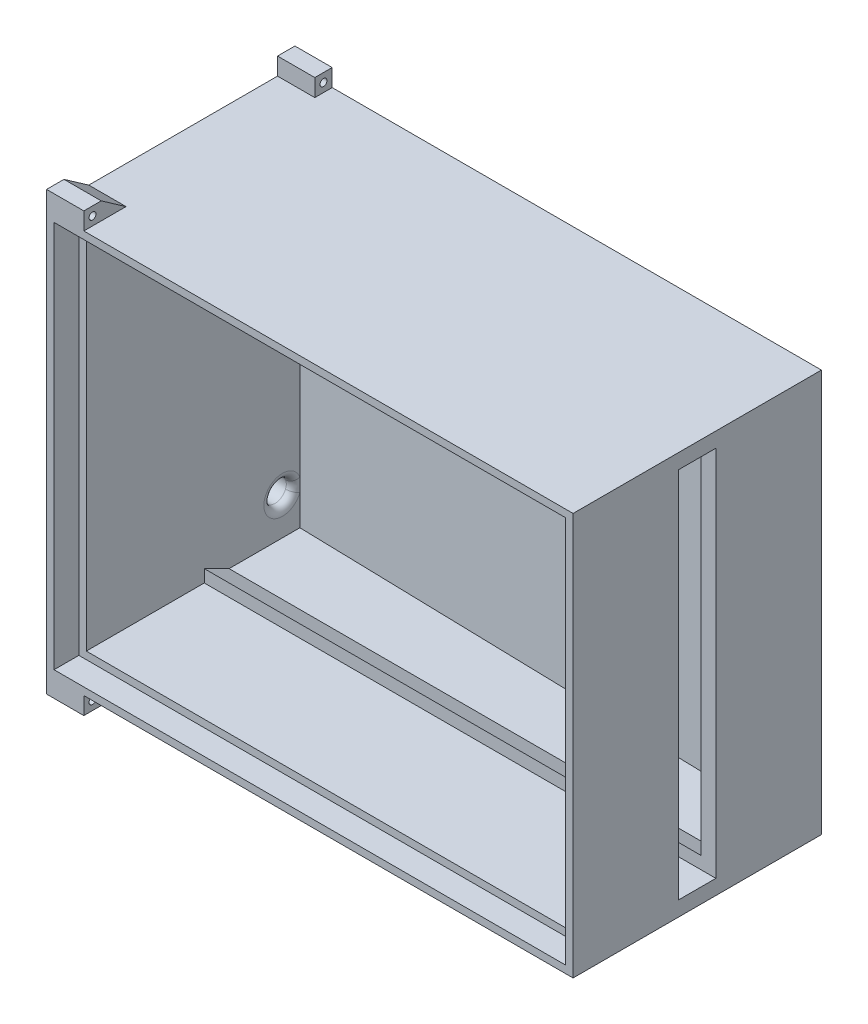
SolidWorks part; units mm, degrees
ref_plane "Front Plane" through (0, 0, 0) normal (0, 0, 1) x (1, 0, 0)
ref_plane "Top Plane" through (0, 0, 0) normal (0, 1, 0) x (1, 0, 0)
ref_plane "Right Plane" through (0, 0, 0) normal (1, 0, 0) x (0, 0, -1)
sketch "Sketch1" plane through (0, 0, 0) normal (0, 0, 1) x (1, 0, 0)
  line L5 (100, 75) -> (-100, 75)
  line L6 (100, 75) -> (100, -75)
  line L7 (100, -75) -> (-100, -75)
  line L8 (-100, 75) -> (-100, -75)
  line L9 (100, 75) -> (-100, -75) construction
  line L10 (100, -75) -> (-100, 75) construction
  line L11 (106, 81) -> (-106, 81)
  line L12 (106, 81) -> (106, -81)
  line L13 (106, -81) -> (-106, -81)
  line L14 (-106, 81) -> (-106, -81)
  line L15 (106, 81) -> (-106, -81) construction
  line L16 (106, -81) -> (-106, 81) construction
  point P0 (0, 0)
  point P7 (0, 0)
  dimension "D1" = 150
  dimension "D2" = 200
  dimension "D3" = 212
  dimension "D4" = 162
extrude "Boss-Extrude1" add sketch "Sketch1" along normal blind 100
extrude "Boss-Extrude2" add sketch "Sketch1<4>" along normal blind 4 contours L5 L8 L7 L6 region at (0, 0, 0)
sketch "Sketch1<4>" plane through (0, 0, 0) normal (0, 0, 1) x (1, 0, 0) same geometry as "Sketch1"
sketch "Sketch2" plane through (0, 0, 100) normal (0, 0, 1) x (1, 0, 0)
  line L1 (103, 78) -> (-103, 78)
  line L2 (103, 78) -> (103, -78)
  line L3 (103, -78) -> (-103, -78)
  line L4 (-103, 78) -> (-103, -78)
  line L5 (103, 78) -> (-103, -78) construction
  line L6 (103, -78) -> (-103, 78) construction
  point P0 (0, 0)
  line M9 (-100, -75) -> (-100, 75)
  line M10 (-100, 75) -> (100, 75)
  line M11 (100, 75) -> (100, -75)
  line M12 (100, -75) -> (-100, -75)
  dimension "D1" = 156
  dimension "D2" = 206
extrude "Cut-Extrude1" cut sketch "Sketch2" against normal blind 10 contours L1 L4 L3 L2 M12 M9 M10 M11 region at (100.416, 0, 100)
sketch "Sketch3" plane through (106, 0, 0) normal (1, 0, 0) x (0, 0, -1)
  line L0 (-50, 81) -> (-50, -81)
  line L1 (-100, 81) -> (0, 81) construction
  line L2 (-100, -81) -> (0, -81) construction
  line L4 (-42.5, 75) -> (-57.5, 75)
  line L5 (-42.5, 75) -> (-42.5, -75)
  line L6 (-42.5, -75) -> (-57.5, -75)
  line L7 (-57.5, 75) -> (-57.5, -75)
  line L8 (-42.5, 75) -> (-57.5, -75) construction
  line L9 (-42.5, -75) -> (-57.5, 75) construction
  point P6 (-50, 0)
  dimension "D1" = 150
  dimension "D2" = 15
extrude "Cut-Extrude2" cut sketch "Sketch3" against normal blind 200 contours L6 L7 L4 L5
sketch "Sketch4" plane through (100, 0, 0) normal (-1, 0, 0) x (0, 0, 1)
  line L0 (42.5, 75) -> (42.5, 70)
  line L1 (42.5, -75) -> (42.5, 75) construction
  line L2 (42.5, 70) -> (32.5, 75)
  line L3 (90, 75) -> (4, 75) construction
  line L4 (32.5, 75) -> (42.5, 75)
  line L6 (32.5, -75) -> (42.5, -75)
  line L7 (42.5, -70) -> (32.5, -75)
  line L8 (42.5, -75) -> (42.5, -70)
  dimension "D1" = 10
  dimension "D2" = 5
extrude "Boss-Extrude3" add sketch "Sketch4" along normal blind 200
sketch "Sketch5" plane through (0, 75, 0) normal (0, -1, 0) x (1, 0, 0)
  line L0 (100, 9) -> (-100, 4)
  line L1 (100, 32.5) -> (100, 4) construction
  line L2 (-100, 32.5) -> (-100, 4) construction
  line L3 (100, 4) -> (-100, 4) construction
  line L4 (-100, 4) -> (100, 4)
  line L5 (100, 4) -> (100, 9)
  dimension "D1" = 5
extrude "Boss-Extrude4" add sketch "Sketch5" along normal blind 150
sketch "Sketch6" plane through (-106, 0, 0) normal (-1, 0, 0) x (0, 0, 1)
  line L0 (50, 81) -> (50, -81)
  line L1 (100, 81) -> (0, 81) construction
  line L2 (100, -81) -> (0, -81) construction
  line L3 (32.5, -75) -> (4, -75) construction
  line L5 (4, 75) -> (4, -75) construction
  line L6 (0, 81) -> (7, 81)
  line L7 (0, 81) -> (0, 88)
  line L8 (0, 88) -> (7, 88)
  line L9 (7, 81) -> (7, 88)
  line L13 (3.5, 88) -> (3.5, 81) construction
  line L14 (100, 81) -> (83, 81)
  line L16 (100, 88) -> (93, 88)
  line L17 (100, 81) -> (100, 88)
  line L19 (83, 81) -> (93, 88)
  line L20 (100, 0) -> (0, 0) construction
  line L21 (100, 81) -> (100, -81) construction
  line L22 (3.5, -88) -> (3.5, -81) construction
  line L23 (83, -81) -> (93, -88)
  line L24 (100, -81) -> (100, -88)
  line L25 (100, -88) -> (93, -88)
  line L26 (100, -81) -> (83, -81)
  line L27 (7, -81) -> (7, -88)
  line L28 (0, -88) -> (7, -88)
  line L29 (0, -81) -> (0, -88)
  line L30 (0, -81) -> (7, -81)
  circle A0 centre (67.5, -51) radius 1.4
  circle A1 centre (67.5, -32) radius 1.4
  circle A4 centre (32.5, -32) radius 1.4
  circle A5 centre (32.5, -51) radius 1.4
  circle A6 centre (67.5, -32) radius 3
  circle A7 centre (67.5, -51) radius 3
  circle A8 centre (32.5, -51) radius 3
  circle A9 centre (32.5, -32) radius 3
  circle A10 centre (42.5, 31) radius 1.4
  circle A11 centre (42.5, -13) radius 1.4
  circle A12 centre (57.5, -13) radius 1.4
  circle A13 centre (57.5, 31) radius 1.4
  circle A14 centre (42.5, 31) radius 3
  circle A15 centre (42.5, -13) radius 3
  circle A16 centre (57.5, -13) radius 3
  circle A17 centre (57.5, 31) radius 3
  circle A18 centre (11, -60) radius 5.75
  circle A19 centre (11, -60) radius 4.5
  circle A20 centre (14.5, 31) radius 1.4
  circle A21 centre (14.5, 31) radius 3
  circle A22 centre (14.5, -13) radius 1.4
  circle A23 centre (14.5, -13) radius 3
  circle A24 centre (85.5, -13) radius 3
  circle A25 centre (85.5, -13) radius 1.4
  circle A26 centre (85.5, 31) radius 1.4
  circle A27 centre (85.5, 31) radius 3
  circle A28 centre (3.5, 84.5) radius 1.4
  circle A29 centre (96.5, 84.5) radius 1.4
  circle A30 centre (96.5, -84.5) radius 1.4
  circle A31 centre (3.5, -84.5) radius 1.4
  line M3 (0, -81) -> (100, -81)
  line M5 (100, 81) -> (0, 81)
  dimension "D1" = 19
  dimension "D2" = 35
  dimension "D3" = 30
  dimension "D4" = 2.8
  dimension "D5" = 50
  dimension "D6" = 28
  dimension "D7" = 50
  dimension "D8" = 15
  dimension "D9" = 11.5
  dimension "D10" = 9
  dimension "D11" = 15
  dimension "D12" = 7
  dimension "D13" = 2.8
  dimension "D14" = 35
  dimension "D15" = 44
  dimension "D16" = 44
  dimension "D19" = 2.8
  dimension "D20" = 2.8
  dimension "D21" = 15
  dimension "D17" = 7
  dimension "D18" = 7
extrude "Boss-Extrude5" add sketch "Sketch6" along normal blind 3 contours A17 A13 | A14 A10 | A16 A12 | A15 A11 | A6 A1 | A7 A0 | A8 A5 | A9 A4 | A21 A20 | A23 A22 | A24 A25 | A27 A26 region at (-106, -32, 64.5849) region at (-106, -51, 64.5849) region at (-106, -51, 29.5849) region at (-106, -32, 29.5849) region at (-106, 31, 39.5849) region at (-106, -13, 39.5849) region at (-106, -13, 54.5849) region at (-106, 31, 54.5849) region at (-106, 31, 11.5849) region at (-106, -13, 11.5849) region at (-106, -13, 82.5849) region at (-106, 31, 82.5849)
extrude "Cut-Extrude3" cut sketch "Sketch6<3>" against normal blind 4 contours A13 | A10 | A11 | A12 | A1 | A4 | A5 | A0 region at (-106, -51, 67.5) region at (-106, -32, 67.5) region at (-106, -32, 32.5) region at (-106, -51, 32.5) region at (-106, 31, 42.5) region at (-106, -13, 42.5) region at (-106, -13, 57.5) region at (-106, 31, 57.5)
sketch "Sketch6<3>" plane through (-106, 0, 0) normal (-1, 0, 0) x (0, 0, 1) same geometry as "Sketch6"
extrude "Cut-Extrude4" cut sketch "Sketch6<5>" against normal blind 6 contours A19 region at (-106, -60, 11)
sketch "Sketch6<5>" plane through (-106, 0, 0) normal (-1, 0, 0) x (0, 0, 1) same geometry as "Sketch6"
extrude "Boss-Extrude6" add sketch "Sketch6<6>" along normal blind 10 contours A18 A19 region at (-106, -60, 5.4126)
sketch "Sketch6<6>" plane through (-106, 0, 0) normal (-1, 0, 0) x (0, 0, 1) same geometry as "Sketch6"
fillet "Fillet1" radius 3 1 edges at (-100, -64.5, 11)
extrude "Boss-Extrude7" add sketch "Sketch6<8>" against normal blind 15 contours L19 L17 L16 A29 M5 | L9 L8 L7 A28 M5 | L25 L24 L23 A30 M3 | L29 L28 L27 A31 M3 region at (-106, -83.9754, 93.4276) region at (-106, -84.5, 6.901) region at (-106, 83.9754, 93.4276) region at (-106, 81.099, 3.5)
sketch "Sketch6<8>" plane through (-106, 0, 0) normal (-1, 0, 0) x (0, 0, 1) same geometry as "Sketch6"
